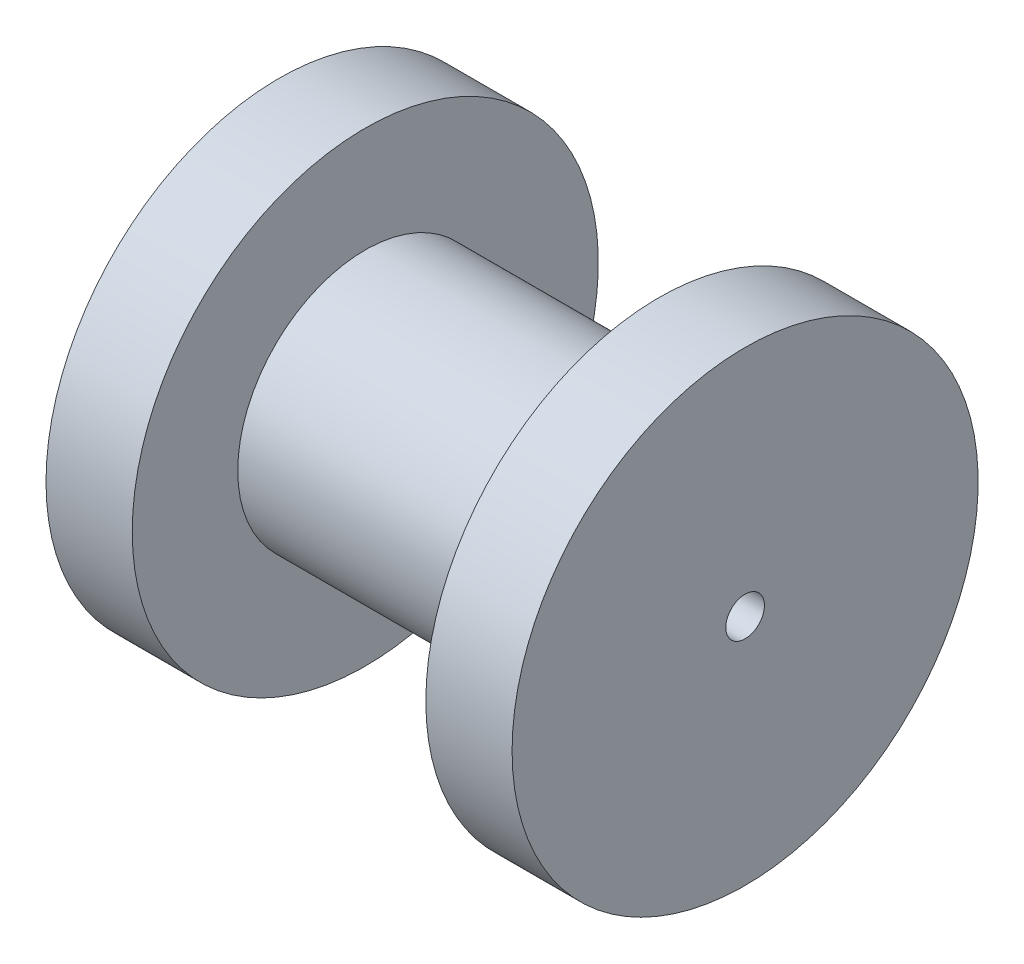
SolidWorks part; units mm, degrees
ref_plane "Front" through (0, 0, 0) normal (0, 0, 1) x (1, 0, 0)
ref_plane "Top" through (0, 0, 0) normal (0, 1, 0) x (1, 0, 0)
ref_plane "Right" through (0, 0, 0) normal (1, 0, 0) x (0, 0, -1)
ref_axis "side-side" through (80.9, 0, 0) along (-1, 0, 0)
ref_axis "up-down" through (0, 50, 0) along (0, -1, 0)
ref_axis "front-back" through (0, 0, -80.9) along (0, 0, 1)
sketch "Sketch1" plane through (0, 0, 0) normal (0, 1, 0) x (1, 0, 0)
  line L1 (-14.0504, -18.23) -> (-8, -18.23)
  line L3 (-8, -18.23) -> (-8, -12.48)
  line L5 (-8, -12.48) -> (8, -12.48)
  line L7 (8, -12.48) -> (8, -18.23)
  line L9 (8, -18.23) -> (13.3445, -18.23)
  point P6 (-14.0504, -18.23)
  point P8 (13.3445, -18.23)
sketch "Sketch2" plane through (0, 0, 0) normal (0, 1, 0) x (1, 0, 0)
  line L0 (0, 0) -> (30.8368, 0) construction
  line L1 (8, -12.7) -> (12.7, -12.7)
  line L2 (-12.7, -12.7) -> (-8, -12.7)
  line L3 (-8, -12.7) -> (-8, -6.95)
  line L4 (-8, -6.95) -> (8, -6.95)
  line L5 (8, -12.7) -> (8, -6.95)
  line L6 (8, -12.48) -> (8, -18.23) construction
  line L7 (-8, -18.23) -> (-8, -12.48) construction
  line L8 (-12.7, -12.7) -> (-12.7, -1.0541)
  line L9 (12.7, -12.7) -> (12.7, -1.0541)
  line L10 (-12.7, -1.0541) -> (12.7, -1.0541)
  point P15 (0, 0)
  point P16 (0, 0)
  point P17 (12.7, -2.1536)
  dimension "D1" = 25.4
  dimension "D2" = 25.4
  dimension "D3" = 2.1082
revolve "Revolve1" add sketch "Sketch2" angle 360 about L0
